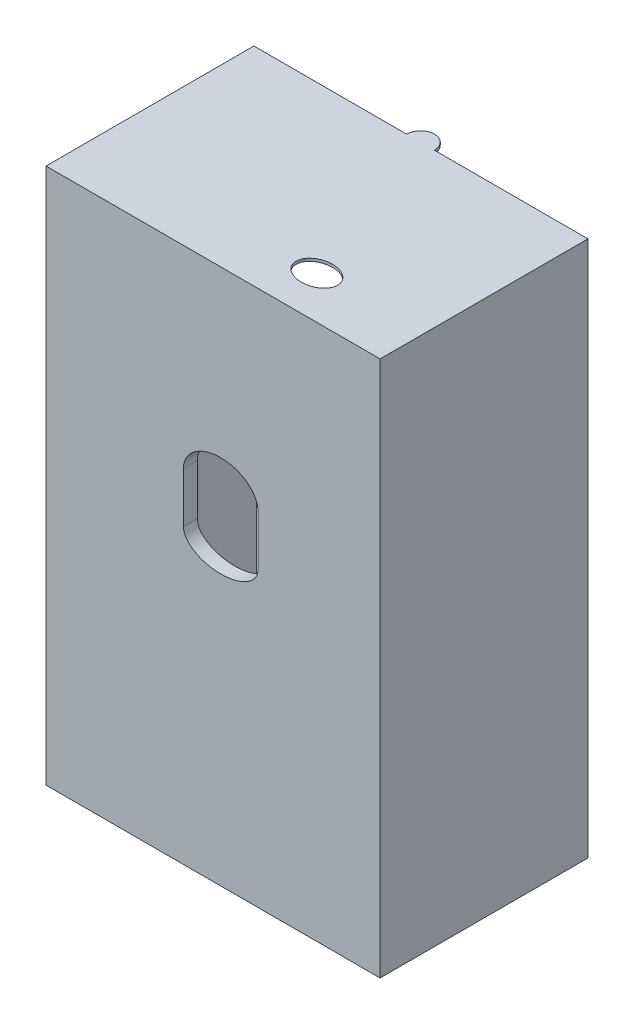
SolidWorks part; units mm, degrees
note: The reader was unsure of these and kept them because the rebuilt part matched: shared geometry of "Sketch1<3>", "Sketch4<2>".
material "ABS"
ref_plane "Front Plane" through (0, 0, 0) normal (0, 0, 1) x (1, 0, 0)
ref_plane "Top Plane" through (0, 0, 0) normal (0, 1, 0) x (1, 0, 0)
ref_plane "Right Plane" through (0, 0, 0) normal (1, 0, 0) x (0, 0, -1)
sketch "Sketch1" plane through (0, 0, 0) normal (0, 0, 1) x (1, 0, 0)
  line L0 (-60.2322, 96.6546) -> (60.2848, 96.6546)
  line L4 (-60.2322, -96.7687) -> (60.2848, -96.7687)
  line L5 (60.2848, 96.6546) -> (60.2848, -96.7687)
  line L6 (-60.2322, 96.6546) -> (-60.2322, -96.7687)
  line L8 (-59.2322, 95.6546) -> (59.2848, 95.6546)
  line L9 (59.2848, 95.6546) -> (59.2848, -95.7687)
  line L10 (-59.2322, -95.7687) -> (59.2848, -95.7687)
  line L11 (-59.2322, 95.6546) -> (-59.2322, -95.7687)
  dimension "D1" = 1
extrude "Boss-Extrude1" add sketch "Sketch1" along normal blind 75 contours L0 L5 L4 L6
extrude "Cut-Extrude1" cut sketch "Sketch1<3>" along normal blind 70 contours L8 L11 L10 L9
sketch "Sketch1<3>" plane through (0, 0, 0) normal (0, 0, 1) x (1, 0, 0) same geometry as "Sketch1"
sketch "Sketch2" plane through (0, 96.6546, 0) normal (0, 1, 0) x (1, 0, 0)
  line L0 (-60.2322, 0) -> (60.2848, 0) construction
  arc A0 (4.8788, 0) -> (-5.1207, 0) centre (-0.121, 0.051) ccw
  line M1 (60.2848, 0) -> (-60.2322, 0)
extrude "Boss-Extrude2" add sketch "Sketch2" against normal blind 1 contours A0 M1
sketch "Sketch4" plane through (0, 0, 70) normal (0, 0, -1) x (-1, 0, 0)
  line L0 (-16.2367, 8.8038) -> (-16.2367, 26.9663)
  line L1 (10.6546, 8.8038) -> (10.6546, 26.9663)
  ellipse E1 centre (-2.7911, 26.9663) end of major axis (-16.2367, 26.9663) minor radius 10.0763 (10.6546, 26.9663) -> (-16.2367, 26.9663) ccw
  ellipse E2 centre (-2.7911, 8.8038) end of major axis (-16.2367, 8.8038) minor radius 8.077 (-16.2367, 8.8038) -> (10.6546, 8.8038) ccw
extrude "Cut-Extrude4" cut sketch "Sketch4<2>" against normal through all both and the other way through all
sketch "Sketch4<2>" plane through (0, 0, 70) normal (0, 0, -1) x (-1, 0, 0) same geometry as "Sketch4"
sketch "Sketch6" plane through (0, 96.6546, 0) normal (0, 1, 0) x (1, 0, 0)
  spline S0 degree 3 poles (14.6071, -59.2541) (14.6071, -59.9964) (14.6558, -60.3607) (14.7979, -60.8972) (14.8568, -61.0743) (14.9984, -61.4253) (15.0815, -61.5999) (15.3647, -62.1131) (15.5953, -62.4362) (16.0022, -62.8933) (16.148, -63.041) (16.4607, -63.327) (16.6272, -63.4648) (17.1475, -63.8549) (17.5249, -64.0873) (18.1366, -64.3943) (18.3495, -64.4901) (18.7844, -64.6645) (19.0061, -64.7431) (19.6834, -64.9537) (20.1514, -65.0607) (21.121, -65.206) (21.611, -65.2421) (22.3438, -65.2426) (22.5883, -65.2339) (23.0775, -65.1983) (23.3236, -65.1711) (24.0483, -65.0636) (24.516, -64.9575) (25.4213, -64.6776) (25.8621, -64.5016) (26.6769, -64.0944) (27.0552, -63.8626) (27.578, -63.472) (27.7452, -63.3341) (28.0575, -63.0496) (28.2034, -62.9024) (28.6111, -62.4463) (28.8439, -62.1218) (29.2233, -61.4375) (29.3653, -61.0868) (29.5092, -60.5482) (29.5456, -60.3666) (29.5946, -59.9991) (29.6069, -59.8133) (29.6075, -59.2616) (29.5601, -58.8974) (29.4175, -58.3566) (29.3575, -58.1764) (29.2146, -57.8224) (29.1321, -57.6494) (28.8519, -57.1416) (28.6222, -56.8182) (28.2113, -56.3563) (28.0638, -56.2072) (27.7529, -55.9231) (27.4249, -55.6515) (27.0628, -55.405) (26.6835, -55.1712) (26.484, -55.0601) (25.8697, -54.7521) (25.4387, -54.5794) (24.5347, -54.2979) (24.0569, -54.1888) (23.0959, -54.0451) (22.6097, -54.0086) (21.8717, -54.0079) (21.6232, -54.0168) (21.1335, -54.0526) (20.8912, -54.0794) (20.1722, -54.1859) (19.7022, -54.2918) (18.787, -54.5749) (18.3553, -54.7477) (17.7451, -55.0522) (17.548, -55.1613) (17.1667, -55.395) (16.9823, -55.5199) (16.4607, -55.9099) (16.1504, -56.1925) (15.6042, -56.8027) (15.3685, -57.1323) (14.9932, -57.809) (14.8502, -58.1593) (14.6563, -58.8842) (14.6071, -59.2541) (14.6071, -59.9964) (14.6558, -60.3607) knots -0.03125 -0.03125 0 0 0.03125 0.03125 0.046875 0.046875 0.0625 0.0625 0.09375 0.09375 0.109375 0.109375 0.125 0.125 0.15625 0.15625 0.171875 0.171875 0.1875 0.1875 0.21875 0.21875 0.25 0.25 0.265625 0.265625 0.28125 0.28125 0.3125 0.3125 0.34375 0.34375 0.375 0.375 0.390625 0.390625 0.40625 0.40625 0.4375 0.4375 0.46875 0.46875 0.484375 0.484375 0.5 0.5 0.53125 0.53125 0.546875 0.546875 0.5625 0.5625 0.59375 0.59375 0.609375 0.609375 0.625 0.640625 0.640625 0.65625 0.65625 0.6875 0.6875 0.71875 0.71875 0.75 0.75 0.765625 0.765625 0.78125 0.78125 0.8125 0.8125 0.84375 0.84375 0.859375 0.859375 0.875 0.875 0.90625 0.90625 0.9375 0.9375 0.96875 0.96875 1 1 1.03125 1.03125 1.046875 only from (14.6071, -59.6253) to (14.6071, -59.6253) construction
  spline S1 degree 3 poles (14.6071, -59.2541) (14.6071, -59.9964) (14.6558, -60.3607) (14.7979, -60.8972) (14.8568, -61.0743) (14.9984, -61.4253) (15.0815, -61.5999) (15.3647, -62.1131) (15.5953, -62.4362) (16.0022, -62.8933) (16.148, -63.041) (16.4607, -63.327) (16.6272, -63.4648) (17.1475, -63.8549) (17.5249, -64.0873) (18.1366, -64.3943) (18.3495, -64.4901) (18.7844, -64.6645) (19.0061, -64.7431) (19.6834, -64.9537) (20.1514, -65.0607) (21.121, -65.206) (21.611, -65.2421) (22.3438, -65.2426) (22.5883, -65.2339) (23.0775, -65.1983) (23.3236, -65.1711) (24.0483, -65.0636) (24.516, -64.9575) (25.4213, -64.6776) (25.8621, -64.5016) (26.6769, -64.0944) (27.0552, -63.8626) (27.578, -63.472) (27.7452, -63.3341) (28.0575, -63.0496) (28.2034, -62.9024) (28.6111, -62.4463) (28.8439, -62.1218) (29.2233, -61.4375) (29.3653, -61.0868) (29.5092, -60.5482) (29.5456, -60.3666) (29.5946, -59.9991) (29.6069, -59.8133) (29.6075, -59.2616) (29.5601, -58.8974) (29.4175, -58.3566) (29.3575, -58.1764) (29.2146, -57.8224) (29.1321, -57.6494) (28.8519, -57.1416) (28.6222, -56.8182) (28.2113, -56.3563) (28.0638, -56.2072) (27.7529, -55.9231) (27.4249, -55.6515) (27.0628, -55.405) (26.6835, -55.1712) (26.484, -55.0601) (25.8697, -54.7521) (25.4387, -54.5794) (24.5347, -54.2979) (24.0569, -54.1888) (23.0959, -54.0451) (22.6097, -54.0086) (21.8717, -54.0079) (21.6232, -54.0168) (21.1335, -54.0526) (20.8912, -54.0794) (20.1722, -54.1859) (19.7022, -54.2918) (18.787, -54.5749) (18.3553, -54.7477) (17.7451, -55.0522) (17.548, -55.1613) (17.1667, -55.395) (16.9823, -55.5199) (16.4607, -55.9099) (16.1504, -56.1925) (15.6042, -56.8027) (15.3685, -57.1323) (14.9932, -57.809) (14.8502, -58.1593) (14.6563, -58.8842) (14.6071, -59.2541) (14.6071, -59.9964) (14.6558, -60.3607) knots -0.03125 -0.03125 0 0 0.03125 0.03125 0.046875 0.046875 0.0625 0.0625 0.09375 0.09375 0.109375 0.109375 0.125 0.125 0.15625 0.15625 0.171875 0.171875 0.1875 0.1875 0.21875 0.21875 0.25 0.25 0.265625 0.265625 0.28125 0.28125 0.3125 0.3125 0.34375 0.34375 0.375 0.375 0.390625 0.390625 0.40625 0.40625 0.4375 0.4375 0.46875 0.46875 0.484375 0.484375 0.5 0.5 0.53125 0.53125 0.546875 0.546875 0.5625 0.5625 0.59375 0.59375 0.609375 0.609375 0.625 0.640625 0.640625 0.65625 0.65625 0.6875 0.6875 0.71875 0.71875 0.75 0.75 0.765625 0.765625 0.78125 0.78125 0.8125 0.8125 0.84375 0.84375 0.859375 0.859375 0.875 0.875 0.90625 0.90625 0.9375 0.9375 0.96875 0.96875 1 1 1.03125 1.03125 1.046875 only from (14.6071, -59.6253) to (14.6071, -59.6253)
extrude "Cut-Extrude6" cut sketch "Sketch6" against normal mid plane 20
extrude "Cut-Extrude3" cut sketch "Sketch4" against normal mid plane 20
